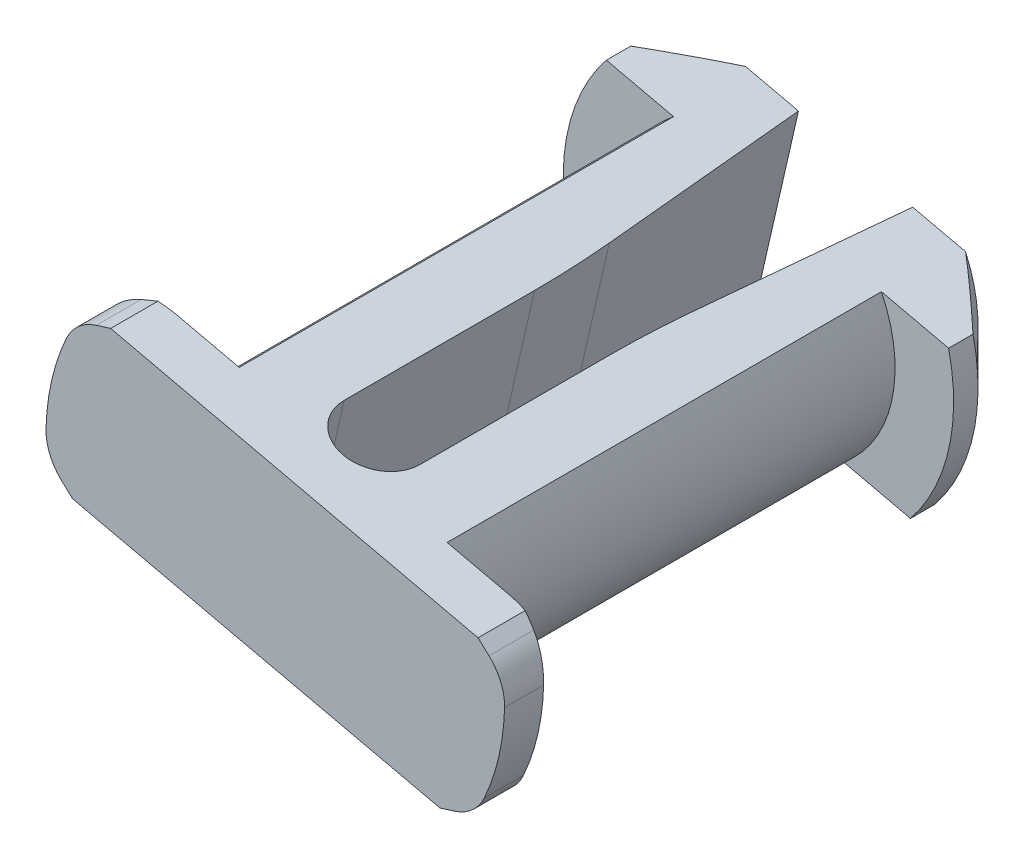
SolidWorks part; units mm, degrees
ref_plane "Front Plane" through (0, 0, 0) normal (0, 0, 1) x (1, 0, 0)
ref_plane "Top Plane" through (0, 0, 0) normal (0, 1, 0) x (1, 0, 0)
ref_plane "Right Plane" through (0, 0, 0) normal (1, 0, 0) x (0, 0, -1)
sketch "Sketch2" plane through (0, 0, 0) normal (0, 0, 1) x (1, 0, 0)
  line L9 (-55.221, 10.852) -> (-53.8702, 10.5426)
  line L10 (-54.4396, 14.2637) -> (-55.221, 10.852)
  line L11 (-53.0889, 13.9543) -> (-54.4396, 14.2637)
  line L22 (-58.1314, 11.5186) -> (-56.7806, 11.2092)
  line L23 (-56.7806, 11.2092) -> (-55.9992, 14.6209)
  line L24 (-55.9992, 14.6209) -> (-57.35, 14.9302)
  circle A3 centre (-55.6101, 12.7364) radius 3
  circle A5 centre (-55.6101, 12.7364) radius 5
  arc A7 (-53.8702, 10.5426) -> (-53.0889, 13.9543) centre (-55.6101, 12.7364) ccw
  arc A9 (-57.35, 14.9302) -> (-58.1314, 11.5186) centre (-55.6101, 12.7364) ccw
ref_plane "Plane1" through (0, 0, 7.5) normal (0, 0, 1) x (1, 0, 0)
sketch "Sketch3" plane through (0, 0, 7.5) normal (0, 0, 1) x (1, 0, 0)
  line L0 (-59.4714, 15.4161) -> (-50.9675, 13.4684)
  line L2 (-60.2528, 12.0044) -> (-51.7489, 10.0568)
  line L3 (-54.4396, 14.2637) -> (-53.0889, 13.9543) construction
  line L4 (-53.8702, 10.5426) -> (-55.221, 10.852) construction
  arc A1 (-51.7489, 10.0568) -> (-50.9675, 13.4684) centre (-55.6101, 12.7364) ccw
  arc A2 (-59.4714, 15.4161) -> (-60.2528, 12.0044) centre (-55.6101, 12.7364) ccw
  circle A7 centre (-55.6101, 12.7364) radius 5 construction
  dimension "D1" = 0.3
extrude "Boss-Extrude1" add sketch "Sketch3" against normal blind 1
chamfer "Chamfer1" distance 0.5 angle 30 4 edges at (-51.7489, 10.0568, 7) (-50.9675, 13.4684, 7) (-60.2528, 12.0044, 7) (-59.4714, 15.4161, 7) first distance on face at (-56.0008, 11.0306, 7) first distance on face at (-55.2194, 14.4423, 7)
fillet "Fillet1" radius 1 4 edges at (-50.9231, 13.0859, 7) (-51.5425, 10.3818, 7) (-60.2971, 12.3869, 7) (-59.6778, 15.091, 7)
ref_axis "Axis1" through (-55.6101, 12.7364, 6.5) along (0, 0, 1)
ref_plane "Plane2" through (0, 0, 0) normal (0.2233, 0.9748, 0) x (0.9748, -0.2233, 0)
sketch "Sketch5" plane through (0, 0, 0) normal (0.2233, 0.9748, 0) x (0.9748, -0.2233, 0)
  line L0 (-61.75, -6.5) -> (-61.75, -7.5) construction
  line L1 (-53.1879, -6.5) -> (-60.9121, -6.5) construction
  line L2 (-60.95, -6.5) -> (-61.75, -6.5)
  line L3 (-61.75, -6.5) -> (-61.75, -6.7)
  arc A0 (-61.75, -6.7) -> (-60.95, -6.5) centre (-60.95, -8.2) cw
  dimension "D1" = 0.2
  dimension "D2" = 0.8
revolve "Cut-Revolve1" cut sketch "Sketch5" angle 360 about axis through (-55.6101, 12.7364, 6.5) along (0, 0, 1)
sketch "Sketch6" plane through (0, 0, 6.5) normal (0, 0, -1) x (-1, 0, 0)
  line L0 (58.1314, 11.5186) -> (56.7806, 11.2092) construction
  line L1 (55.9992, 14.6209) -> (57.35, 14.9302) construction
  line L2 (56.7806, 11.2092) -> (55.9992, 14.6209) construction
  line L3 (55.221, 10.852) -> (53.8702, 10.5426) construction
  line L4 (54.4396, 14.2637) -> (55.221, 10.852) construction
  line L5 (53.0889, 13.9543) -> (54.4396, 14.2637) construction
  line L6 (58.1314, 11.5186) -> (56.7806, 11.2092)
  line L7 (55.9992, 14.6209) -> (57.35, 14.9302)
  line L8 (56.7806, 11.2092) -> (55.9992, 14.6209)
  line L9 (55.221, 10.852) -> (53.8702, 10.5426)
  line L10 (54.4396, 14.2637) -> (55.221, 10.852)
  line L11 (53.0889, 13.9543) -> (54.4396, 14.2637)
  arc A0 (58.1314, 11.5186) -> (57.35, 14.9302) centre (55.6101, 12.7364) ccw construction
  arc A1 (53.0889, 13.9543) -> (53.8702, 10.5426) centre (55.6101, 12.7364) ccw construction
  arc A2 (58.1314, 11.5186) -> (57.35, 14.9302) centre (55.6101, 12.7364) ccw
  arc A3 (53.0889, 13.9543) -> (53.8702, 10.5426) centre (55.6101, 12.7364) ccw
extrude "Boss-Extrude2" add sketch "Sketch6" along normal blind 8.9
sketch "Sketch7" plane through (0, 0, -2.4) normal (0, 0, -1) x (-1, 0, 0)
  line L0 (54.4396, 14.2637) -> (51.7133, 13.6392)
  line L1 (51.8221, 13.6642) -> (53.0889, 13.9543) construction
  line L2 (55.221, 10.852) -> (52.4947, 10.2276)
  line L3 (53.8702, 10.5426) -> (52.6035, 10.2525) construction
  line L4 (54.4396, 14.2637) -> (55.221, 10.852)
  line L5 (54.4396, 14.2637) -> (55.9992, 14.6209) construction
  line L6 (55.2194, 14.4423) -> (56.0008, 11.0306) construction
  line L7 (55.9992, 14.6209) -> (58.7255, 15.2453)
  line L8 (56.7806, 11.2092) -> (59.5069, 11.8336)
  line L9 (55.9992, 14.6209) -> (56.7806, 11.2092)
  arc A0 (52.4947, 10.2276) -> (51.7133, 13.6392) centre (55.6101, 12.7364) cw
  circle A1 centre (55.6101, 12.7364) radius 3 construction
  arc A2 (59.5069, 11.8336) -> (58.7255, 15.2453) centre (55.6101, 12.7364) ccw
  dimension "D1" = 1
extrude "Boss-Extrude3" add sketch "Sketch7" along normal blind 1.6
sketch "Sketch8" plane through (0, 0, 0) normal (0.2233, 0.9748, 0) x (0.9748, -0.2233, 0)
  line L0 (-61.05, 2.9) -> (-59.95, 4)
  line L1 (-61.05, 4) -> (-61.05, 2.4) construction
  line L2 (-60.6469, 4) -> (-57.85, 4) construction
  line L3 (-59.95, 4) -> (-61.05, 4)
  line L4 (-61.05, 4) -> (-61.05, 2.9)
  line L5 (-61.05, 2.4) -> (-60.6469, 2.4) construction
  dimension "D1" = 0.5
revolve "Cut-Revolve2" cut sketch "Sketch8" angle 360 about axis through (-55.6101, 12.7364, 6.5) along (0, 0, 1)
sketch "Sketch9" plane through (0.3907, 1.7058, 0) normal (0.2233, 0.9748, 0) x (0.9748, -0.2233, 0)
  line L0 (-58.25, 4) -> (-57.85, -1)
  line L1 (-59.3625, 4) -> (-57.85, 4) construction
  line L2 (-57.85, 4) -> (-57.85, -6.5) construction
  line L3 (-57.85, -1) -> (-57.85, 4)
  line L4 (-57.85, 4) -> (-58.25, 4)
  line L5 (-57.05, -6.5) -> (-57.05, 4) construction
  line L6 (-56.25, -6.5) -> (-57.85, -6.5) construction
  line L7 (-57.05, -6.5) -> (-57.05, -7.5) construction
  line L8 (-56.25, 4) -> (-54.7375, 4) construction
  line L9 (-55.85, 4) -> (-56.25, -1)
  line L10 (-56.25, 4) -> (-55.85, 4)
  line L11 (-56.25, -1) -> (-56.25, 4)
  dimension "D1" = 5
  dimension "D2" = 0.4
extrude "Cut-Extrude1" cut sketch "Sketch9" against normal through all both and the other way through all
fillet "Fillet2" radius 20 2 edges at (-54.8303, 12.5578, 1) (-56.3899, 12.915, 1)
fillet "Fillet3" 2 edges at (-56.3899, 12.915, 6.5) (-54.8303, 12.5578, 6.5) type full round first side face at (-56.3899, 12.915, 4.1494) second side face at (-54.8303, 12.5578, 4.1494) middle face at (-55.6101, 12.7364, 6.5)
